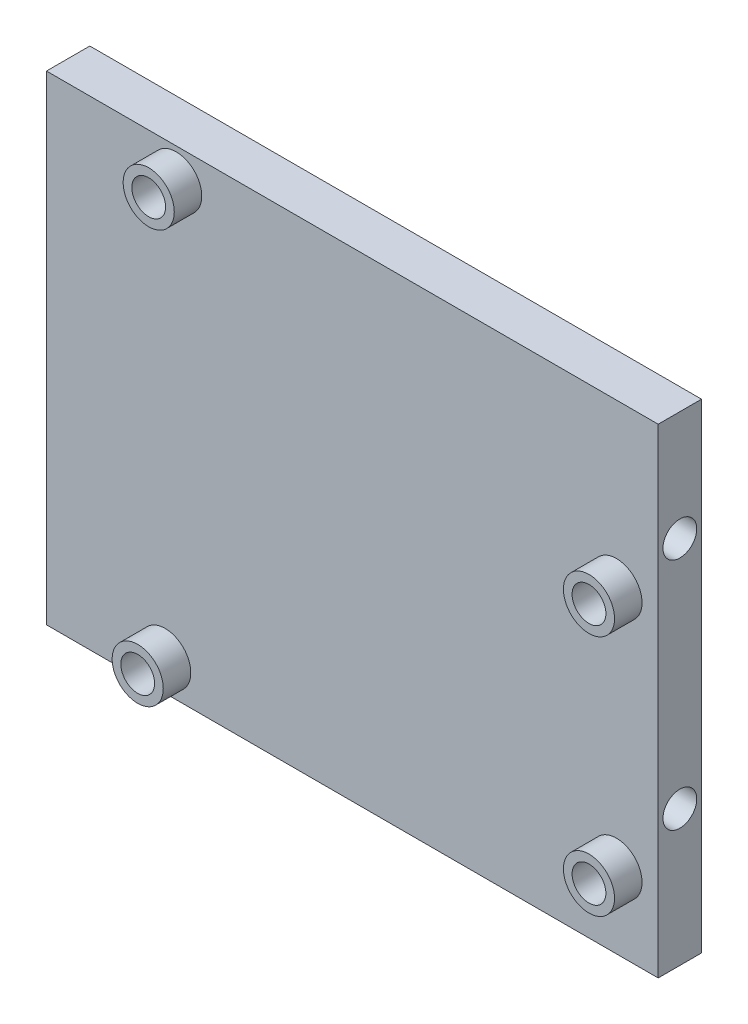
SolidWorks part; units mm, degrees
ref_plane "Front Plane" through (0, 0, 0) normal (0, 0, 1) x (1, 0, 0)
ref_plane "Top Plane" through (0, 0, 0) normal (0, 1, 0) x (1, 0, 0)
ref_plane "Right Plane" through (0, 0, 0) normal (1, 0, 0) x (0, 0, -1)
sketch "Sketch1" plane through (0, 0, 0) normal (0, 0, 1) x (1, 0, 0)
  line L0 (0, 26.67) -> (0, -26.67) construction
  line L6 (-35.29, -27.67) -> (35.29, -27.67)
  line L7 (-34.29, 0) -> (34.29, 0) construction
  line L8 (31.75, 26.67) -> (-34.29, 26.67) construction
  line L9 (-34.29, 26.67) -> (-34.29, -26.67) construction
  line L10 (-34.29, -26.67) -> (31.75, -26.67) construction
  line L11 (31.75, -26.67) -> (31.75, -13.716) construction
  line L12 (31.75, -13.716) -> (34.29, -11.176) construction
  line L13 (34.29, -11.176) -> (34.29, 21.59) construction
  line L14 (34.29, 21.59) -> (31.75, 24.13) construction
  line L15 (31.75, 24.13) -> (31.75, 26.67) construction
  line L16 (-35.29, -27.67) -> (-35.29, 27.67)
  line L17 (-35.29, 27.67) -> (35.29, 27.67)
  line L18 (35.29, -27.67) -> (35.29, 27.67)
  line L19 (-35.29, -27.67) -> (35.29, 27.67) construction
  line L20 (-35.29, 27.67) -> (35.29, -27.67) construction
  circle A6 centre (-20.32, 24.13) radius 1.95
  circle A8 centre (30.48, 8.89) radius 1.95
  circle A9 centre (30.48, -19.05) radius 1.95
  circle A10 centre (-21.59, -24.13) radius 1.95
  point P0 (0, 0)
  point P6 (0, 0)
  dimension "D3" = 3.9
  dimension "D1" = 1
  dimension "D2" = 1
extrude "Boss-Extrude1" add sketch "Sketch1" along normal mid plane 5
sketch "Sketch3" plane through (0, 0, 2.5) normal (0, 0, 1) x (1, 0, 0)
  circle A0 centre (-20.32, 24.13) radius 2.95
  circle A7 centre (30.48, -19.05) radius 1.95
  circle A10 centre (-20.32, 24.13) radius 1.95
  circle A12 centre (30.48, 8.89) radius 1.95
  circle A14 centre (-21.59, -24.13) radius 2.95
  circle A15 centre (30.48, 8.89) radius 2.95
  circle A16 centre (30.48, -19.05) radius 2.95
  circle A18 centre (-21.59, -24.13) radius 1.95
  dimension "D1" = 1
  dimension "D2" = 3.9
extrude "Boss-Extrude2" add sketch "Sketch3" along normal blind 3.175
sketch "Sketch4" plane through (35.29, 0, 0) normal (1, 0, 0) x (0, 0, -1)
  line L0 (0, 0) -> (-50000, 0) construction
  line L1 (0, 0) -> (0, 50000) construction
  circle A0 centre (0, 15) radius 1.95
  circle A1 centre (0, -12) radius 1.95
  point P9 (0, 0)
  dimension "D1" = 3.9
  dimension "D2" = 15
  dimension "D3" = 12
extrude "Cut-Extrude2" cut sketch "Sketch4" against normal blind 5.5
